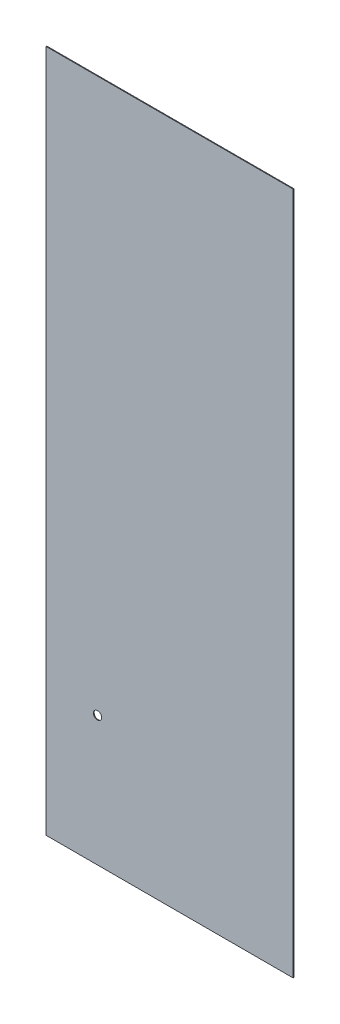
SolidWorks part; units mm, degrees
ref_plane "Front Plane" through (0, 0, 0) normal (0, 0, 1) x (1, 0, 0)
ref_plane "Top Plane" through (0, 0, 0) normal (0, 1, 0) x (1, 0, 0)
ref_plane "Right Plane" through (0, 0, 0) normal (1, 0, 0) x (0, 0, -1)
sketch "Sketch1" plane through (0, 0, 0) normal (0, 0, 1) x (1, 0, 0)
  line L1 (0, 0) -> (240, 0)
  line L2 (0, 0) -> (0, 663.4)
  line L3 (0, 663.4) -> (240, 663.4)
  line L4 (240, 0) -> (240, 663.4)
  dimension "D1" = 663.4
  dimension "D2" = 240
base flange "Base-Flange1" sketch "Sketch1" thickness 0.7 reverse thickness direction no parameters "D1"=0.7
sketch "Sketch2" plane through (0, 0, -0.7) normal (0, 0, -1) x (-1, 0, 0)
  line L0 (0, 0) -> (-240, 0) construction
  line L1 (0, 663.4) -> (0, 0) construction
  circle A0 centre (-50, 125.84) radius 4
  dimension "D1" = 125.84
  dimension "D2" = 50
  dimension "D3" = 8
extrude "Cut-Extrude1" cut sketch "Sketch2" against normal blind 10 normal cut yes
sketch "Bend-Lines1" [suppressed] plane through (0, 0, 0) normal (0, 1, 0) x (1, 0, 0)
sketch "Bounding-Box1" [suppressed] plane through (0, 0, 0) normal (0, 1, 0) x (1, 0, 0)
sheet metal parameters "Sheet-Metal1" thickness 0.7 parameters "D1"=0.7
flat pattern "Flat-Pattern1" [suppressed]
sketch "Bend-Lines2" plane through (0, 0, 0) normal (0, 1, 0) x (1, 0, 0)
sketch3d "Bounding-Box2" [suppressed]
  line L0 (240, 663.4, 0) -> (240, 0, 0) construction
  line L1 (0, 663.4, 0) -> (0, 0, 0) construction
  line L2 (240, 663.4, 0) -> (0, 663.4, 0) construction
  line L3 (240, 0, 0) -> (0, 0, 0) construction
sheet metal parameters "Sheet-Metal2" thickness 0.7 parameters "D1"=0.7
flat pattern "Flat-Pattern1"
sketch "Bend-Lines2" plane through (0, 0, 0) normal (0, 1, 0) x (1, 0, 0)
sketch3d "Bounding-Box2" [suppressed]
  line L0 (240, 663.4, 0) -> (240, 0, 0) construction
  line L1 (0, 663.4, 0) -> (0, 0, 0) construction
  line L2 (240, 663.4, 0) -> (0, 663.4, 0) construction
  line L3 (240, 0, 0) -> (0, 0, 0) construction
